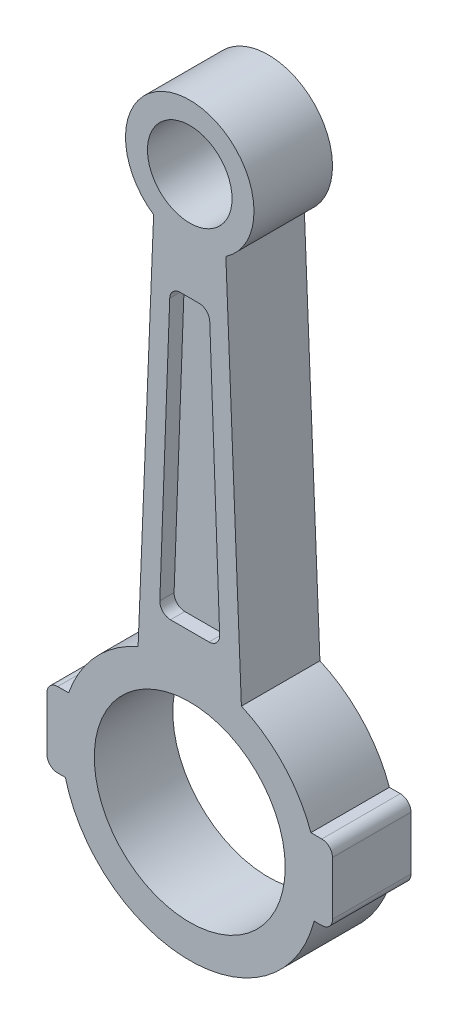
SolidWorks part; units mm, degrees
ref_plane "Front Plane" through (0, 0, 0) normal (0, 0, 1) x (1, 0, 0)
ref_plane "Top Plane" through (0, 0, 0) normal (0, 1, 0) x (1, 0, 0)
ref_plane "Right Plane" through (0, 0, 0) normal (1, 0, 0) x (0, 0, -1)
other "Configuration Table"
sketch "Sketch1" plane through (0, 0, 0) normal (0, 0, 1) x (1, 0, 0)
  circle A0 centre (0, 0) radius 36
extrude "Big End" add sketch "Sketch1" along normal mid plane 22
sketch "Sketch2" plane through (0, 0, 0) normal (0, 0, 1) x (1, 0, 0)
  circle A0 centre (0, 154.8) radius 18
extrude "Small End" add sketch "Sketch2" along normal mid plane 22
sketch "Sketch3" plane through (0, 0, 0) normal (0, 0, 1) x (1, 0, 0)
  line L0 (-15, 20) -> (15, 20)
  line L1 (15, 20) -> (10, 142.8)
  line L2 (10, 142.8) -> (-10, 142.8)
  line L3 (-10, 142.8) -> (-15, 20)
extrude "Beam" add sketch "Sketch3" along normal mid plane 22
sketch "Sketch4" plane through (0, 0, 0) normal (0, 0, 1) x (1, 0, 0)
  line L0 (29, -9) -> (37, -9)
  line L1 (40, -6) -> (40, 9)
  line L2 (37, 12) -> (29, 12)
  line L3 (26, 9) -> (26, -6)
  line L4 (-37, -9) -> (-29, -9)
  line L5 (-26, -6) -> (-26, 9)
  line L6 (-29, 12) -> (-37, 12)
  line L7 (-40, 9) -> (-40, -6)
  arc A0 (26, -6) -> (29, -9) centre (29, -6) ccw
  arc A1 (37, -9) -> (40, -6) centre (37, -6) ccw
  arc A2 (40, 9) -> (37, 12) centre (37, 9) ccw
  arc A3 (29, 12) -> (26, 9) centre (29, 9) ccw
  arc A4 (-40, -6) -> (-37, -9) centre (-37, -6) ccw
  arc A5 (-29, -9) -> (-26, -6) centre (-29, -6) ccw
  arc A6 (-26, 9) -> (-29, 12) centre (-29, 9) ccw
  arc A7 (-37, 12) -> (-40, 9) centre (-37, 9) ccw
extrude "Cap Bolt Bosses" add sketch "Sketch4" along normal mid plane 22
sketch "Sketch5" plane through (0, 0, 0) normal (0, 0, 1) x (1, 0, 0)
  line L0 (-5.3865, 44) -> (5.3865, 44)
  line L1 (8.3845, 47.1113) -> (5.6073, 121.9113)
  line L2 (2.6093, 124.8) -> (-2.6093, 124.8)
  line L3 (-5.6073, 121.9113) -> (-8.3845, 47.1113)
  arc A0 (-8.3845, 47.1113) -> (-5.3865, 44) centre (-5.3865, 47) ccw
  arc A1 (5.3865, 44) -> (8.3845, 47.1113) centre (5.3865, 47) ccw
  arc A2 (5.6073, 121.9113) -> (2.6093, 124.8) centre (2.6093, 121.8) ccw
  arc A3 (-2.6093, 124.8) -> (-5.6073, 121.9113) centre (-2.6093, 121.8) ccw
extrude "Beam Pocket Front" cut sketch "Sketch5" along normal blind 5 from offset 7
sketch "Sketch6" plane through (0, 0, 0) normal (0, 0, 1) x (1, 0, 0)
  line L0 (-5.3865, 44) -> (5.3865, 44)
  line L1 (8.3845, 47.1113) -> (5.6073, 121.9113)
  line L2 (2.6093, 124.8) -> (-2.6093, 124.8)
  line L3 (-5.6073, 121.9113) -> (-8.3845, 47.1113)
  arc A0 (-8.3845, 47.1113) -> (-5.3865, 44) centre (-5.3865, 47) ccw
  arc A1 (5.3865, 44) -> (8.3845, 47.1113) centre (5.3865, 47) ccw
  arc A2 (5.6073, 121.9113) -> (2.6093, 124.8) centre (2.6093, 121.8) ccw
  arc A3 (-2.6093, 124.8) -> (-5.6073, 121.9113) centre (-2.6093, 121.8) ccw
extrude "Beam Pocket Rear" cut sketch "Sketch6" along normal blind 5 from offset 12 offset against normal yes
sketch "Sketch7" plane through (0, 0, 0) normal (0, 0, 1) x (1, 0, 0)
  circle A0 centre (0, 0) radius 26.75
extrude "Big End Bore" cut sketch "Sketch7" against normal through all and the other way through all
sketch "Sketch8" plane through (0, 0, 0) normal (0, 0, 1) x (1, 0, 0)
  circle A0 centre (0, 154.8) radius 11.85
extrude "Small End Bore" cut sketch "Sketch8" against normal through all and the other way through all
ref_axis "Big End Axis" through (0, 0, -199.0801) along (0, 0, 1)
sketch3d "Small End Axis Line"
  line L0 (0, 154.8, -11) -> (0, 154.8, 11)
ref_axis "Small End Axis" through (0, 154.8, -11) along (0, 0, 1)
